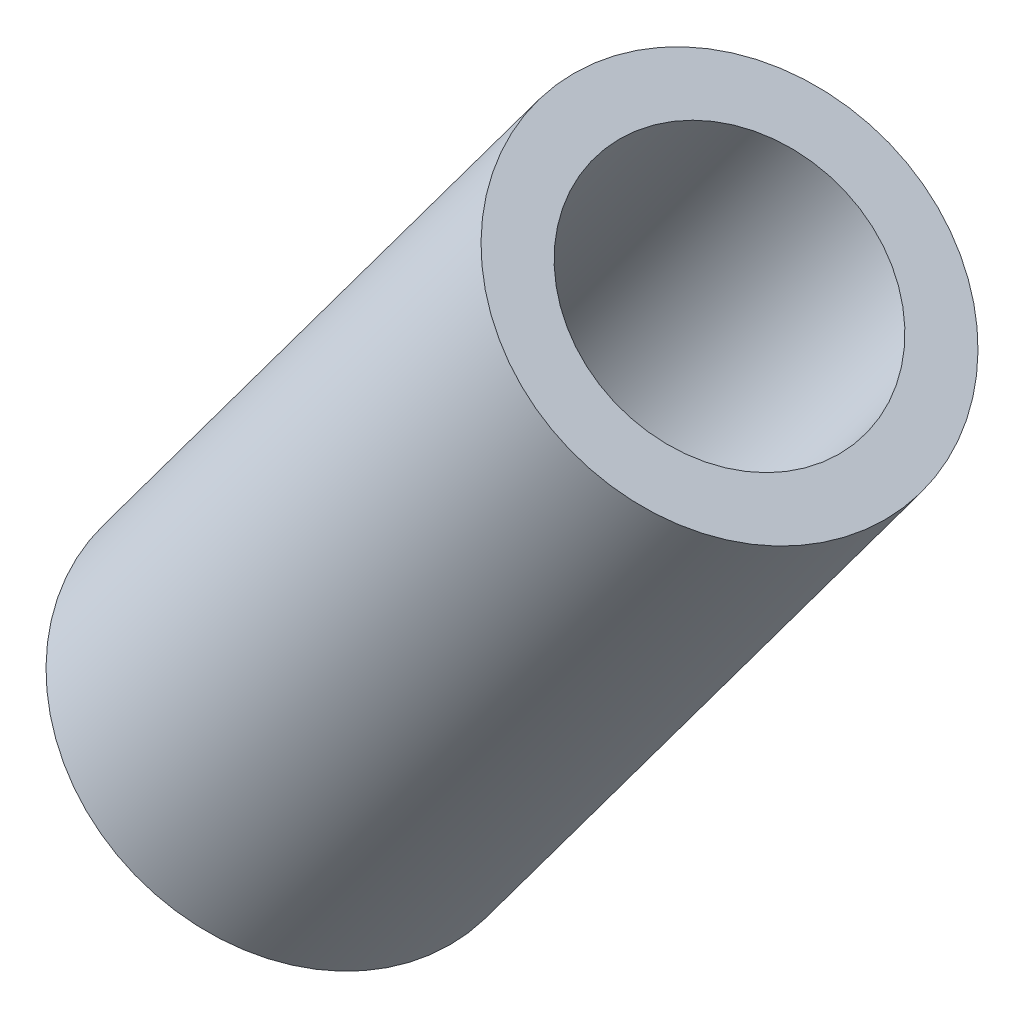
SolidWorks part; units mm, degrees
material "Silicon Rubber"
ref_plane "X-Y Datum" through (0, 0, 0) normal (0, 0, 1) x (1, 0, 0)
ref_plane "X-Z Datum" through (0, 0, 0) normal (0, 1, 0) x (1, 0, 0)
ref_plane "Y-Z Datum" through (0, 0, 0) normal (1, 0, 0) x (0, 0, -1)
sketch3d "3DSketch1"
  line L0 (0, 0, 0) -> (30.2901, 40.7817, 0)
  dimension "D1" = 50.8
sweep "Sweep1" add path "3DSketch1" circular profile diameter 26.9875 parameters "D3"=26.9875
sweep "Cut-Sweep1" cut path "3DSketch1<2>" circular profile diameter 19.05 parameters "D3"=19.05
sketch3d "3DSketch1<2>" same geometry as "3DSketch1"
sketch3d "3DSketch2"
  line L0 (0, 0, 0) -> (30.2901, 40.7817, 0) construction
  circle A1 centre (15.1451, 20.3909, 0) radius 9.525 construction
  circle A4 centre (30.2901, 40.7817, 0) radius 9.525 construction
  point P1 (0, 0, 0)
  point P4 (9.4657, 12.7443, 0)
  point P8 (24.6107, 33.1351, 0)
  point P9 (15.1451, 20.3909, 0)
